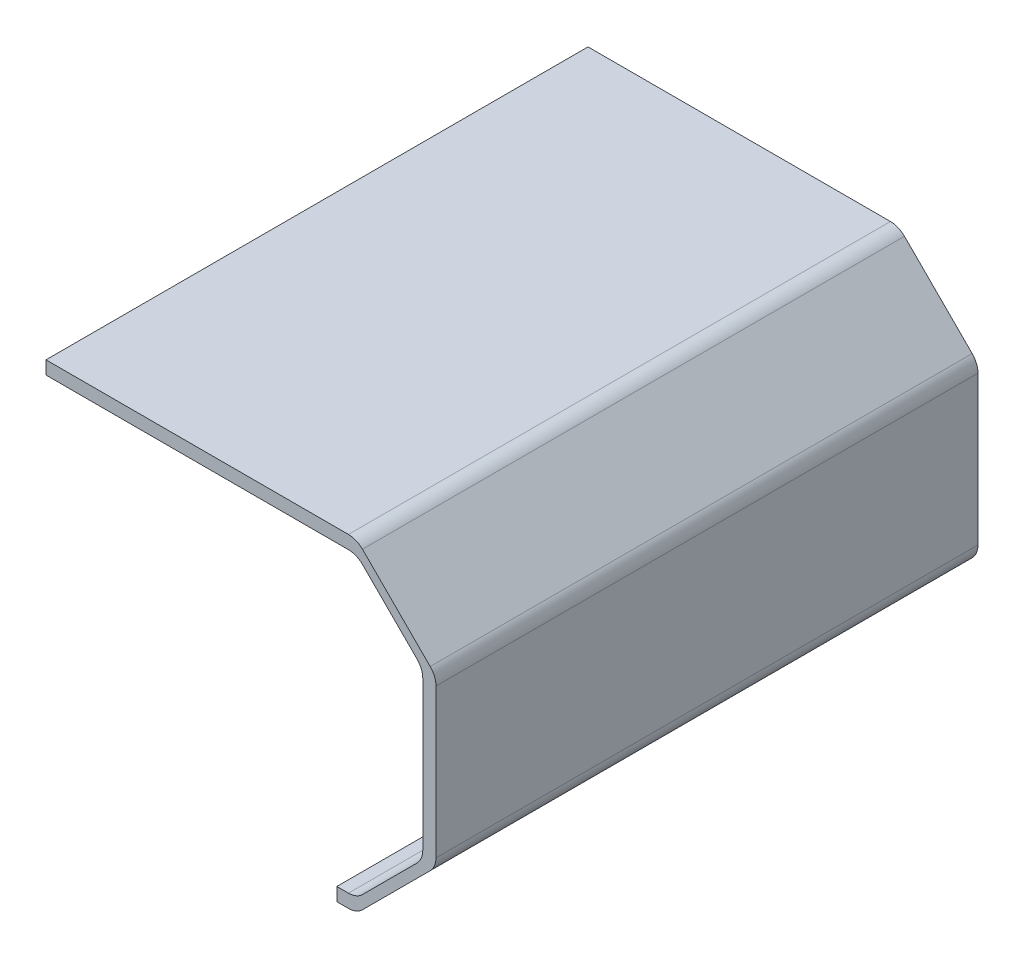
SolidWorks part; units mm, degrees
ref_plane "前视基准面" through (0, 0, 0) normal (0, 0, 1) x (1, 0, 0)
ref_plane "上视基准面" through (0, 0, 0) normal (0, 1, 0) x (1, 0, 0)
ref_plane "右视基准面" through (0, 0, 0) normal (1, 0, 0) x (0, 0, -1)
sketch "草图1" plane through (0, 0, 0) normal (0, 0, 1) x (1, 0, 0)
  line L0 (0, 0) -> (0, 2)
  line L1 (0, 2) -> (3, 2)
  line L5 (-44, 49) -> (3, 49)
  line L7 (0, 0) -> (3, 0)
  line L13 (3, 47) -> (-44, 47)
  line L15 (3, 2) -> (13, 12)
  line L16 (3, 0) -> (15, 12)
  line L17 (13, 37) -> (13, 12)
  line L18 (15, 12) -> (15, 37)
  line L19 (3, 47) -> (13, 37)
  line L20 (3, 49) -> (15, 37)
  line L21 (-44, 49) -> (-44, 47)
extrude "凸台-拉伸1" add sketch "草图1" along normal blind 82
fillet "圆角1" radius 3 8 edges at (3, 0, 41) (15, 12, 41) (15, 37, 41) (3, 49, 41) (3, 2, 41) (13, 12, 41) (13, 37, 41) (3, 47, 41)
